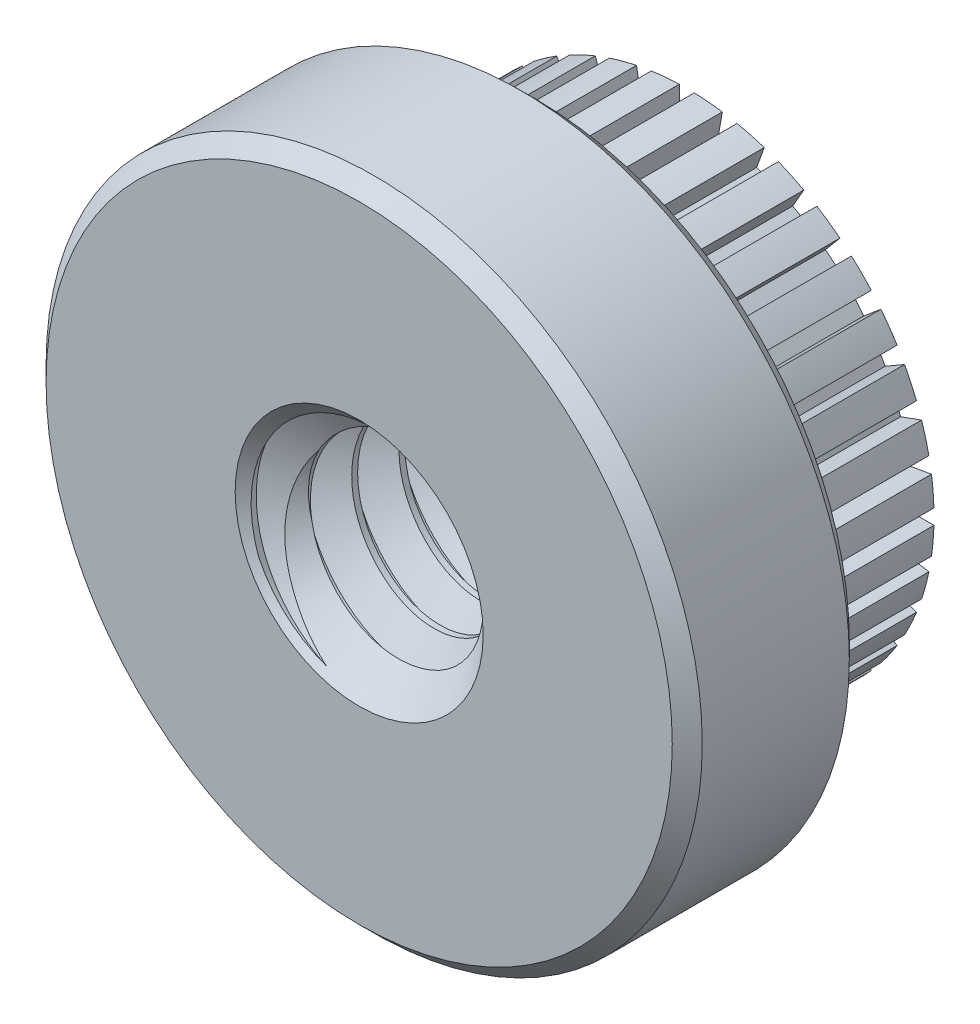
SolidWorks part; units mm, degrees
ref_plane "Front Plane" through (0, 0, 0) normal (0, 0, 1) x (1, 0, 0)
ref_plane "Top Plane" through (0, 0, 0) normal (0, 1, 0) x (1, 0, 0)
ref_plane "Right Plane" through (0, 0, 0) normal (1, 0, 0) x (0, 0, -1)
sketch "Sketch1" plane through (0, 0, 0) normal (0, 0, 1) x (1, 0, 0)
  circle A0 centre (0, 0) radius 2.78
  dimension "A" = 5.56
extrude "Extrude1" add sketch "Sketch1" against normal blind 1.5
sketch "Sketch2" plane through (0, 0, -1.5) normal (0, 0, -1) x (-1, 0, 0)
  circle A0 centre (0, 0) radius 2.095
  dimension "C" = 4.19
extrude "Extrude2" add sketch "Sketch2" along normal blind 1.53
sketch "Sketch3" plane through (0, 0, -3.03) normal (0, 0, -1) x (-1, 0, 0)
  line L0 (0, 1.9045) -> (0, 2.78)
  circle A1 centre (0, 0) radius 2.78 construction
  circle A2 centre (0, 0) radius 1.9045
  circle A3 centre (0, 0) radius 1.9045 construction
  dimension "D1" = 0.1905
extrude "Cut-Extrude-Thin1" cut sketch "Sketch3" against normal up to surface (1.53 mm away) thin up to face at (2.78, 0, -1.5) thin type mid plane wall 0.127
pattern_circular "CirPattern1" count 36 over 360 about axis through (0, 0, -1.5) along (0, 0, 1) of "Cut-Extrude-Thin1"
sketch "Sketch5" plane through (0, 0, -3.03) normal (0, 0, -1) x (-1, 0, 0)
  circle A2 centre (0, 0) radius 1.6505
  circle A3 centre (0, 0) radius 1.6505
  dimension "D1" = 0.254
extrude "Cut-Extrude1" cut sketch "Sketch5" against normal blind 0.254 flip side to cut
chamfer "Chamfer1" distance 0.127 angle 45 1 edges at (-1.6505, 0, -3.03)
sketch "Sketch6" plane through (0, 0, -1.5) normal (0, 0, -1) x (-1, 0, 0)
  circle A0 centre (0, 0) radius 1.6505 construction
  circle A1 centre (0, 0) radius 1.6505
  circle A2 centre (0, 0) radius 2.78 construction
  circle A3 centre (0, 0) radius 2.78
extrude "Cut-Extrude2" cut sketch "Sketch6" along normal blind 0.127
chamfer "Chamfer2" distance 0.127 angle 45 2 edges at (2.78, 0, 0) (2.78, 0, -1.5)
sketch "Sketch7" plane through (0, 0, 0) normal (0, 0, 1) x (1, 0, 0)
  circle A0 centre (0, 0) radius 1
  dimension "Thread Od" = 2
extrude "Cut-Extrude3" cut sketch "Sketch7" against normal through all
sketch "Sketch8" plane through (0, 0, -3.03) normal (0, 0, -1) x (-1, 0, 0)
  circle A0 centre (0, 0) radius 1 construction
  circle A1 centre (0, 0) radius 1
curve "Helix/Spiral1" pitch 0.4 height 4.5 radius 1 centre (0, 0, -3.03) axis (0, 0, 1) start towards (0, 1, 0) parameters "pitch"=0.4
sketch "Sketch9" plane through (0, 0, 0) normal (1, 0, 0) x (0, 0, -1)
  line L0 (3.38, 1) -> (3.23, 0.7402)
  line L1 (3.23, 0.7402) -> (3.18, 0.7402)
  line L2 (3.18, 0.7402) -> (3.03, 1)
  line L3 (3.38, 1) -> (3.03, 1)
  line L4 (3.205, 1) -> (3.205, 0.7402) construction
  line L5 (3.305, 0.8701) -> (3.105, 0.8701) construction
  line L6 (3.03, -1) -> (3.03, 1) construction
  dimension "D1" = 60
  dimension "D2" = 0.05
  dimension "D3" = 0.2
sweep "Sweep1" add profiles "Sketch9" path "Helix/Spiral1"
sketch "Sketch10" plane through (0, 0, 0) normal (0, 0, 1) x (1, 0, 0)
  circle A1 centre (0, 0) radius 2.653
  circle A2 centre (0, 0) radius 2.653
  dimension "D1" = 0
extrude "Cut-Extrude4" cut sketch "Sketch10" along normal through all
sketch "Sketch11" plane through (0, 0, -3.03) normal (0, 0, -1) x (-1, 0, 0)
  circle A0 centre (0, 0) radius 1.5235 construction
  circle A1 centre (0, 0) radius 1.5235
extrude "Cut-Extrude5" cut sketch "Sketch11" along normal through all
sketch "Sketch13" plane through (0, 0, 0) normal (0, 0, 1) x (1, 0, 0)
  circle A2 centre (0, 0) radius 1.0508
  circle A3 centre (0, 0) radius 1.0508
  dimension "D1" = 0.0508
extrude "Cut-Extrude6" cut sketch "Sketch13" against normal through all draft 45
sketch "Sketch14" plane through (0, 0, -3.03) normal (0, 0, -1) x (-1, 0, 0)
  circle A2 centre (0, 0) radius 1.0508
  circle A3 centre (0, 0) radius 1.0508
  dimension "D1" = 0.0508
extrude "Cut-Extrude7" cut sketch "Sketch14" against normal through all draft 45
equation "\"D3@Helix/Spiral1\" = \"B@Extrude1\"+3"
equation "\"D2@Sketch9\" = \"pitch@Helix/Spiral1\"*.125"
equation "\"D3@Sketch9\" = \"pitch@Helix/Spiral1\"*.50"
